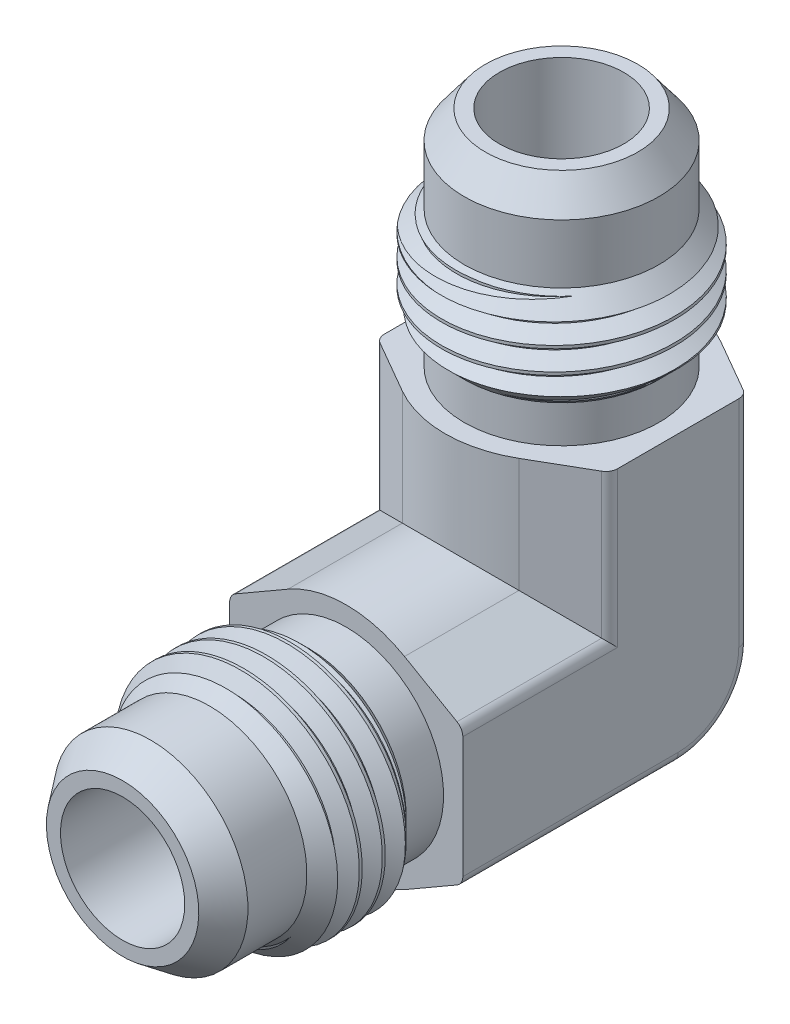
SolidWorks part; units mm, degrees
ref_plane "Front Plane" through (0, 0, 0) normal (0, 0, 1) x (1, 0, 0)
ref_plane "Top Plane" through (0, 0, 0) normal (0, 1, 0) x (1, 0, 0)
ref_plane "Right Plane" through (0, 0, 0) normal (1, 0, 0) x (0, 0, -1)
sketch "Sketch1" plane through (0, 0, 0) normal (1, 0, 0) x (0, 0, -1)
  line L0 (-3.321, -17.037) -> (17.0371, -17.037)
  line L1 (17.0371, -17.037) -> (-17.037, -17.037) construction
  line L2 (17.0371, -17.037) -> (17.0371, 17.0371) construction
  line L3 (17.0371, 17.0371) -> (-17.037, 17.037) construction
  line L4 (-17.037, -17.037) -> (-17.037, 17.037) construction
  line L5 (17.0371, -17.037) -> (-17.037, 17.037) construction
  line L6 (17.0371, 17.0371) -> (-17.037, -17.037) construction
  line L7 (17.0371, -17.037) -> (17.0371, 3.3211)
  line L8 (17.0371, 3.3211) -> (2.7369, 3.3211)
  line L9 (2.7369, 3.3211) -> (2.7369, -2.7368)
  line L10 (2.7369, -2.7368) -> (-3.321, -2.7368)
  line L11 (-3.321, -2.7368) -> (-3.321, -17.037)
  line L12 (-3.321, -9.8869) -> (17.0371, -9.8869) construction
  line L13 (9.887, 3.3211) -> (9.887, -17.037) construction
  line L14 (-17.037, -15.856) -> (-17.037, -3.9179)
  line L15 (-17.037, -13.697) -> (9.8869, -13.697)
  line L16 (-17.037, -13.697) -> (-17.037, -6.077)
  line L17 (-17.037, -6.077) -> (9.8869, -6.0769)
  line L18 (9.8869, -13.697) -> (9.8869, -6.0769)
  line L19 (-17.037, -13.697) -> (9.8869, -6.0769) construction
  line L20 (-17.037, -6.077) -> (9.8869, -13.697) construction
  line L21 (6.0769, 17.0371) -> (13.6969, 17.0371)
  line L22 (6.0769, 17.0371) -> (6.077, -9.8869)
  line L23 (6.077, -9.8869) -> (13.6969, -9.8869)
  line L24 (13.6969, 17.0371) -> (13.6969, -9.8869)
  line L25 (6.0769, 17.0371) -> (13.6969, -9.8869) construction
  line L26 (6.077, -9.8869) -> (13.6969, 17.0371) construction
  line L27 (-17.037, -5.2133) -> (-15.318, -3.9179)
  line L28 (-5.607, -17.0307) -> (-11.703, -17.0307)
  line L29 (-5.607, -17.0307) -> (-5.607, -2.7432)
  line L30 (-5.607, -2.7432) -> (-11.703, -2.7432)
  line L31 (-11.703, -17.0307) -> (-11.703, -2.7432)
  line L32 (-5.607, -17.0307) -> (-11.703, -2.7432) construction
  line L33 (-5.607, -2.7432) -> (-11.703, -17.0307) construction
  line L34 (-17.0371, -15.8559) -> (-11.703, -15.8559)
  line L35 (-17.0371, -15.8559) -> (-17.037, -3.9179)
  line L36 (-17.037, -3.9179) -> (-11.703, -3.9179)
  line L37 (-11.703, -15.8559) -> (-11.703, -3.9179)
  line L38 (-17.0371, -15.8559) -> (-11.703, -3.9179) construction
  line L39 (-17.037, -3.9179) -> (-11.703, -15.8559) construction
  line L40 (-3.321, -15.8559) -> (-5.607, -15.8559)
  line L41 (-3.321, -15.8559) -> (-3.321, -3.9179)
  line L42 (-3.321, -3.9179) -> (-5.607, -3.9179)
  line L43 (-5.607, -15.8559) -> (-5.607, -3.9179)
  line L44 (-3.321, -15.8559) -> (-5.607, -3.9179) construction
  line L45 (-3.321, -3.9179) -> (-5.607, -15.8559) construction
  line L46 (3.9179, 17.0371) -> (15.8559, 17.0371)
  line L47 (3.9179, 17.0371) -> (3.9179, 11.7031)
  line L48 (3.9179, 11.7031) -> (15.8559, 11.7031)
  line L49 (15.8559, 17.0371) -> (15.8559, 11.7031)
  line L50 (2.7432, 5.6071) -> (17.0307, 5.6071)
  line L51 (2.7432, 5.6071) -> (2.7432, 11.7031)
  line L52 (2.7432, 11.7031) -> (17.0307, 11.7031)
  line L53 (17.0307, 5.6071) -> (17.0307, 11.7031)
  line L54 (3.9179, 3.3211) -> (15.8559, 3.3211)
  line L55 (3.9179, 3.3211) -> (3.918, 5.6071)
  line L56 (3.918, 5.6071) -> (15.8559, 5.6071)
  line L57 (15.8559, 3.3211) -> (15.8559, 5.6071)
  line L58 (14.5606, 17.0371) -> (15.8559, 15.318)
  point P0 (0, 0)
  point P15 (-3.575, -9.8869)
  point P20 (9.887, 3.5751)
  point P25 (-4.464, -9.8869)
  point P26 (-8.655, -9.8869)
  point P31 (-17.037, -9.887)
  point P34 (-14.37, -9.8869)
  point P44 (-10.2919, -17.0307)
  point P45 (9.887, -9.8869)
  point P46 (17.0307, 8.4293)
  point P62 (-17.037, -13.697)
  point P63 (-17.037, -6.077)
  point P90 (9.887, -9.8869)
  dimension "Height" = 26.924
  dimension "Length" = 26.924
  dimension "Center-to-Space" = 13.208
  dimension "Body Height" = 14.3002
  dimension "Thread Length" = 6.096
  dimension "Thread Size" = 14.2875
  dimension "Space" = 2.286
  dimension "Body Diameter" = 11.938
  dimension "D8" = 0
  dimension "Flared Angle" = 37
  dimension "ID" = 7.62
  dimension "D11" = 1.2954
  dimension "Thread Pitch" = 1.4111
  dimension "D2" = 2.8222
  dimension "D12" = 2
sketch "Sketch2" plane through (0, 0, 0) normal (0, 0, 1) x (1, 0, 0)
  line L1 (7.1501, -17.037) -> (-7.1501, -17.037)
  line L2 (7.1501, -17.037) -> (7.1501, -2.7368)
  line L3 (7.1501, -2.7368) -> (-7.1501, -2.7368)
  line L4 (-7.1501, -17.037) -> (-7.1501, -2.7368)
  line L5 (7.1501, -17.037) -> (-7.1501, -2.7368) construction
  line L6 (7.1501, -2.7368) -> (-7.1501, -17.037) construction
  point P0 (0, -9.8869)
  dimension "Width" = 14.3002
ref_plane "Plane1" through (0, -2.7368, 3.321) normal (0, 0, 1) x (1, 0, 0)
sketch "Sketch3" plane through (0, -2.7368, 3.321) normal (0, 0, 1) x (1, 0, 0)
  line L0 (-7.1501, -10.8654) -> (-7.1501, -3.4348)
  line L1 (7.1501, -14.3002) -> (-7.1501, -14.3002) construction
  line L2 (7.1501, -14.3002) -> (7.1501, 0) construction
  line L3 (7.1501, 0) -> (-7.1501, 0) construction
  line L4 (-7.1501, -14.3002) -> (-7.1501, 0) construction
  line L5 (7.1501, -14.3002) -> (-7.1501, 0) construction
  line L6 (7.1501, 0) -> (-7.1501, -14.3002) construction
  line L7 (7.1501, -10.8654) -> (7.1501, -3.4348)
  line L8 (-6.7926, -2.8156) -> (-3.5751, -0.9579)
  line L9 (0, -10.9601) -> (0, -3.3401) construction
  line L10 (3.5751, -0.9579) -> (6.7926, -2.8156)
  line L11 (6.7926, -11.4846) -> (3.5751, -13.3423)
  line L12 (0, -13.1191) -> (0, -1.1811) construction
  line L13 (-3.5751, -13.3423) -> (-6.7926, -11.4846)
  arc A0 (7.1501, -3.4348) -> (6.7926, -2.8156) centre (6.4351, -3.4348) ccw
  arc A1 (7.1501, -10.8654) -> (6.7926, -11.4846) centre (6.4351, -10.8654) cw
  arc A2 (-7.1501, -10.8654) -> (-6.7926, -11.4846) centre (-6.4351, -10.8654) ccw
  arc A3 (-7.1501, -3.4348) -> (-6.7926, -2.8156) centre (-6.4351, -3.4348) cw
  arc A4 (-3.5751, -0.9579) -> (3.5751, -0.9579) centre (0, -7.1501) cw
  arc A5 (3.5751, -13.3423) -> (-3.5751, -13.3423) centre (0, -7.1501) cw
  point P0 (0, -7.1501)
  point P10 (-7.1501, -7.1501)
  point P13 (7.1501, -7.1501)
  point P21 (7.1501, -3.022)
  point P28 (-7.1501, -3.022)
  point P31 (0, 1.1061)
  point P34 (0, -15.4063)
  dimension "D2" = 0.715
  dimension "D3" = 7.1501
  dimension "D1" = 120
extrude "Boss-Extrude1" add sketch "Sketch3" against normal up to vertex (13.208 mm away) up to point (0, -9.8869, -9.887)
sketch "Sketch4" plane through (0, 0, -9.8869) normal (0, 0, -1) x (-1, 0, 0)
  line L0 (-7.1501, -9.8869) -> (7.1501, -9.887) construction
  line L1 (-7.1501, -17.037) -> (-7.1501, -2.7368) construction
  line L2 (7.1501, -17.037) -> (7.1501, -2.7368) construction
sketch "Sketch7" plane through (0, 0, 0) normal (1, 0, 0) x (0, 0, -1)
  line L0 (-3.321, -9.8869) -> (-17.037, -9.887)
  line L1 (-17.037, -9.887) -> (-17.037, -5.2133)
  line L2 (-17.037, -5.2133) -> (-15.318, -3.9179)
  line L3 (-15.318, -3.9179) -> (-11.703, -3.9179)
  line L5 (-11.703, -3.9179) -> (-10.5283, -2.7432)
  line L6 (-5.607, -2.7432) -> (-11.703, -2.7432) construction
  line L7 (-10.5283, -2.7432) -> (-6.7818, -2.7432)
  line L8 (-6.7818, -2.7432) -> (-5.607, -3.9179)
  line L9 (-5.607, -3.9179) -> (-3.321, -3.9179)
  line L10 (-3.321, -3.9179) -> (-3.321, -9.8869)
  line L11 (-3.321, -2.7368) -> (-3.321, -17.037) construction
  line L12 (-11.703, -17.0307) -> (-11.703, -2.7432) construction
  line L13 (-5.607, -17.0307) -> (-5.607, -2.7432) construction
  dimension "D1" = 45
  dimension "D2" = 45
revolve "Revolve3" add sketch "Sketch7" angle 360 about L0
pattern_circular "CirPattern2" count 2 every 90 about axis through (7.1501, -9.8869, -9.8869) along (-1, 0, 0) of bodies 110
combine bodies "Combine2" bodies to combine 110 111
sketch "Sketch8" plane through (0, 0, -9.8869) normal (0, 0, -1) x (-1, 0, 0)
  line L5 (7.1501, -9.8869) -> (-7.1501, -9.8869)
  line L6 (-7.1501, -9.8869) -> (-7.1501, -13.6023)
  line L7 (-6.7926, -14.2215) -> (-3.5751, -16.0791)
  line L8 (3.5751, -16.0791) -> (6.7926, -14.2215)
  line L9 (7.1501, -13.6023) -> (7.1501, -9.8869)
  line L10 (7.1501, -9.8869) -> (-7.1501, -9.8869)
  line L11 (-7.1501, -9.8869) -> (-7.1501, -13.6023)
  line L12 (-6.7926, -14.2215) -> (-3.5751, -16.0791)
  line L13 (3.5751, -16.0791) -> (6.7926, -14.2215)
  line L14 (7.1501, -13.6023) -> (7.1501, -9.8869)
  arc A3 (-7.1501, -13.6023) -> (-6.7926, -14.2215) centre (-6.4351, -13.6023) ccw
  arc A4 (-3.5751, -16.0791) -> (3.5751, -16.0791) centre (0, -9.887) ccw
  arc A5 (6.7926, -14.2215) -> (7.1501, -13.6023) centre (6.4351, -13.6023) ccw
  arc A6 (-7.1501, -13.6023) -> (-6.7926, -14.2215) centre (-6.4351, -13.6023) ccw
  arc A7 (-3.5751, -16.0791) -> (3.5751, -16.0791) centre (0, -9.887) ccw
  arc A8 (6.7926, -14.2215) -> (7.1501, -13.6023) centre (6.4351, -13.6023) ccw
  dimension "D1" = 0
revolve "Revolve4" add sketch "Sketch8" angle 90 about L10
sketch "Sketch9" plane through (0, 0, 0) normal (1, 0, 0) x (0, 0, -1)
  line L0 (9.887, 17.0371) -> (9.8869, -6.0769)
  line L1 (6.0769, 17.0371) -> (13.6969, 17.0371) construction
  line L2 (9.887, 3.3211) -> (9.887, -17.037) construction
  line L3 (-17.037, -9.887) -> (6.077, -9.8869)
  arc A0 (6.077, -9.8869) -> (9.8869, -6.0769) centre (6.0769, -6.0769) ccw
sweep "Cut-Sweep1" cut path "Sketch9" circular profile diameter 7.62 parameters "D3"=7.62
ref_plane "Plane2" through (0, 0, 5.6071) normal (0, 0, -1) x (-1, 0, 0)
sketch "Sketch15" plane through (0, 0, 5.6071) normal (0, 0, -1) x (-1, 0, 0)
  circle A0 centre (0, -9.8869) radius 7.1438 construction
  circle A1 centre (0, -9.8869) radius 7.1438
curve "Helix/Spiral1" pitch 1.4111 height 7.5071 radius 7.1438 centre (0, -9.8869, 5.607) axis (0, 0, 1) start towards (0, 1, 0)
sketch "Sketch16" plane through (0, 0, 0) normal (1, 0, 0) x (0, 0, -1)
  line L0 (-5.6952, -2.5904) -> (-4.2841, -2.5904) construction
  line L1 (-4.2841, -2.5904) -> (-4.9897, -3.8125) construction
  line L2 (-4.9897, -3.8125) -> (-5.6952, -2.5904) construction
  line L3 (-4.9897, -2.5904) -> (-4.9897, -2.7432) construction
  line L4 (-5.607, -2.7432) -> (-4.3723, -2.7432) construction
  line L5 (-5.0779, -3.6597) -> (-4.9015, -3.6597) construction
  line L6 (-4.9897, -3.6597) -> (-4.9897, -3.8125) construction
  line L7 (-4.9897, -2.6668) -> (-5.6511, -2.6668) construction
  line L8 (-4.2841, -2.5904) -> (-5.6511, -2.6668)
  line L9 (-5.6511, -2.6668) -> (-5.0779, -3.6597)
  line L10 (-5.0779, -3.6597) -> (-4.9015, -3.6597)
  line L11 (-4.9015, -3.6597) -> (-4.2841, -2.5904)
  dimension "D1" = 1.4111
  dimension "D2" = 0.1764
sweep "Cut-Sweep2" cut profiles "Sketch16" path "Helix/Spiral1" align with end faces yes
ref_plane "Plane3" through (0, 5.6071, 0) normal (0, -1, 0) x (-1, 0, 0)
sketch "Sketch17" plane through (0, 5.6071, 0) normal (0, -1, 0) x (-1, 0, 0)
  circle A0 centre (0, 9.887) radius 7.1438 construction
  circle A1 centre (0, 9.887) radius 7.1438
curve "Helix/Spiral2" pitch 1.4111 height 7.5071 radius 7.1438 centre (0, 5.607, -9.887) axis (0, 1, 0) start towards (0, 0, -1)
sketch "Sketch18" plane through (0, 0, 0) normal (1, 0, 0) x (0, 0, -1)
  line L0 (17.1835, 5.6952) -> (17.1835, 4.2841) construction
  line L1 (17.1835, 4.2841) -> (15.9614, 4.9897) construction
  line L2 (15.9614, 4.9897) -> (17.1835, 5.6952) construction
  line L3 (15.9614, 4.9897) -> (16.1142, 4.9897) construction
  line L4 (17.0307, 5.607) -> (17.0307, 4.3723) construction
  line L5 (16.1142, 5.0779) -> (16.1142, 4.9015) construction
  line L6 (17.0307, 4.9897) -> (17.1835, 4.9897) construction
  line L7 (17.1071, 4.9897) -> (17.1071, 5.6511) construction
  line L8 (17.1835, 4.2841) -> (17.1071, 5.6511)
  line L9 (17.1071, 5.6511) -> (16.1142, 5.0779)
  line L10 (16.1142, 5.0779) -> (16.1142, 4.9015)
  line L11 (16.1142, 4.9015) -> (17.1835, 4.2841)
  dimension "D1" = 1.4111
  dimension "D2" = 0.1764
sweep "Cut-Sweep3" cut profiles "Sketch18" path "Helix/Spiral2"
equation "\"D11@Sketch1\"=(\"Body Diameter@Sketch1\"-\"ID@Sketch1\")*.3"
equation "\"D2@Sketch3\"=\"Width@Sketch2\"*.05"
equation "\"D3@Sketch3\"=\"Width@Sketch2\"*.5"
equation "\"D3@Cut-Sweep1\"=\"ID@Sketch1\""
equation "\"D4@Helix/Spiral1\"=\"Thread Pitch@Sketch1\""
equation "\"D3@Helix/Spiral1\"=\"Thread Length@Sketch1\"+\"Thread Pitch@Sketch1\""
equation "\"D1@Sketch16\"=\"Thread Pitch@Sketch1\""
equation "\"D2@Sketch16\"=\"D1@Sketch16\"*.125"
equation "\"D4@Helix/Spiral2\"=\"Thread Pitch@Sketch1\""
equation "\"D3@Helix/Spiral2\"=\"Thread Length@Sketch1\"+\"Thread Pitch@Sketch1\""
equation "\"D1@Sketch18\"=\"Thread Pitch@Sketch1\""
equation "\"D2@Sketch18\"=\"D1@Sketch18\"/8"
equation "\"D2@Sketch1\"=\"Thread Pitch@Sketch1\"*2"
